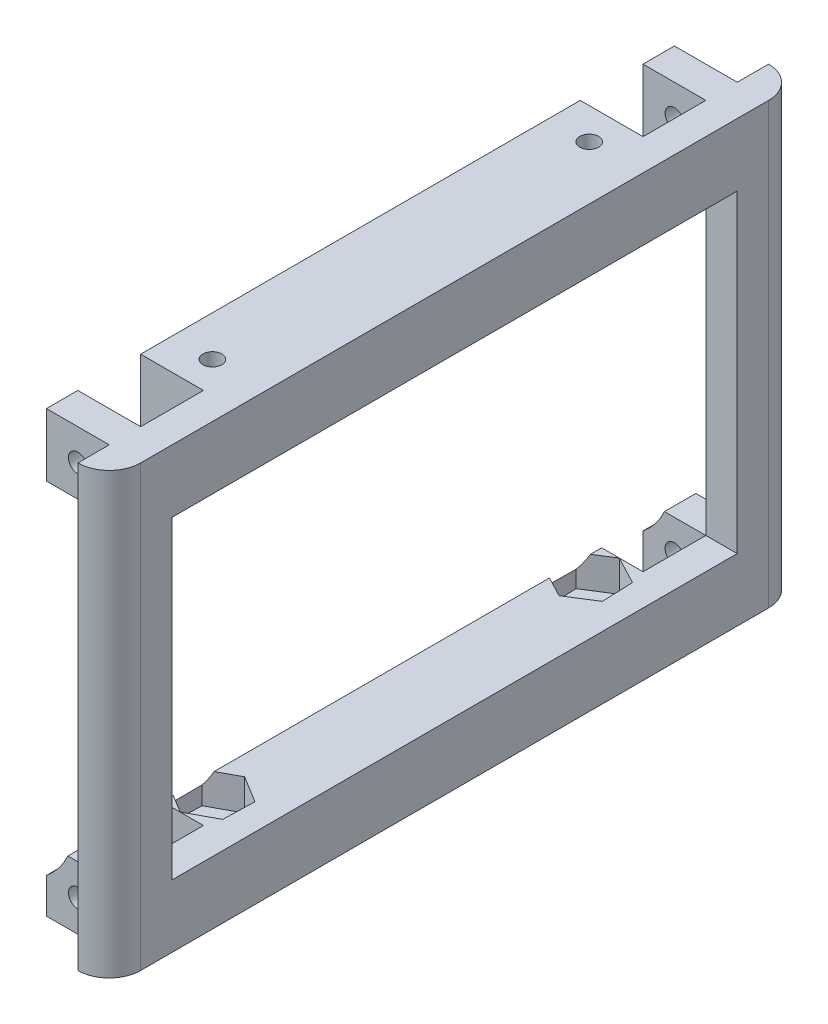
SolidWorks part; units mm, degrees
ref_plane "Front Plane" through (0, 0, 0) normal (0, 0, 1) x (1, 0, 0)
ref_plane "Top Plane" through (0, 0, 0) normal (0, 1, 0) x (1, 0, 0)
ref_plane "Right Plane" through (0, 0, 0) normal (1, 0, 0) x (0, 0, -1)
sketch "Sketch1" plane through (0, 0, 0) normal (1, 0, 0) x (0, 0, -1)
  line L1 (0, 0) -> (110, 0)
  line L2 (0, 0) -> (0, 70)
  line L3 (0, 70) -> (110, 70)
  line L4 (110, 0) -> (110, 70)
  dimension "D1" = 70
  dimension "D2" = 110
extrude "Boss-Extrude1" add sketch "Sketch1" along normal blind 5
fillet "Fillet2" radius 5 1 edges at (5, 35, 0) type face fillet first side face at (2.5, 35, 0) second side face at (5, 35, -55)
fillet "Fillet3" radius 5 1 edges at (5, 35, -110) type face fillet first side face at (5, 35, -57.5) second side face at (2.5, 35, -110)
sketch "Sketch2" plane through (0, 0, 0) normal (-1, 0, 0) x (0, 0, 1)
  line L1 (-105, 70) -> (-100, 70)
  line L2 (-105, 70) -> (-105, 60)
  line L3 (-105, 60) -> (-100, 60)
  line L4 (-100, 70) -> (-100, 60)
  line L5 (-105, 0) -> (-100, 0)
  line L6 (-105, 0) -> (-105, 10)
  line L7 (-105, 10) -> (-100, 10)
  line L8 (-100, 0) -> (-100, 10)
  line L9 (-5, 0) -> (-10, 0)
  line L10 (-5, 0) -> (-5, 10)
  line L11 (-5, 10) -> (-10, 10)
  line L12 (-10, 0) -> (-10, 10)
  line L13 (-5, 70) -> (-10, 70)
  line L14 (-5, 70) -> (-5, 60)
  line L15 (-5, 60) -> (-10, 60)
  line L16 (-10, 70) -> (-10, 60)
  dimension "D1" = 10
  dimension "D2" = 5
  dimension "D3" = 5
  dimension "D4" = 10
  dimension "D5" = 5
extrude "Boss-Extrude2" add sketch "Sketch2" along normal blind 10
sketch "Sketch3" plane through (0, 0, -5) normal (0, 0, 1) x (1, 0, 0)
  circle A0 centre (-5, 65) radius 1.5
  circle A1 centre (-5, 5) radius 1.5
  dimension "D1" = 3
  dimension "D2" = 3
extrude "Cut-Extrude1" cut sketch "Sketch3" against normal blind 122
sketch "Sketch4" plane through (0, 0, 0) normal (-1, 0, 0) x (0, 0, 1)
  line L0 (-100, 70) -> (-10, 70) construction
  line L1 (-90, 70) -> (-20, 70)
  line L2 (-90, 70) -> (-90, 60)
  line L3 (-90, 60) -> (-20, 60)
  line L4 (-20, 70) -> (-20, 60)
  line L5 (-10, 0) -> (-100, 0) construction
  line L6 (-90, 0) -> (-20, 0)
  line L7 (-90, 0) -> (-90, 10)
  line L8 (-90, 10) -> (-20, 10)
  line L9 (-20, 0) -> (-20, 10)
  dimension "D1" = 10
  dimension "D2" = 10
  dimension "D3" = 10
extrude "Boss-Extrude3" add sketch "Sketch4" along normal blind 10
sketch "Sketch5" plane through (0, 0, -5) normal (0, 0, 1) x (1, 0, 0)
  line L0 (-6.5, 5) -> (-17.5, 5) construction
  line L1 (-17.5, 5) -> (-17.5, 15) construction
  circle A0 centre (-5, 5) radius 1.5 construction
  circle A1 centre (-17.5, 15) radius 11.5
  dimension "D3" = 23
  dimension "D1" = 11
  dimension "D2" = 10
extrude "Cut-Extrude2" cut sketch "Sketch5" against normal blind 105
sketch "Sketch6" plane through (0, 0, 0) normal (0, -1, 0) x (1, 0, 0)
  line L1 (-10, -20) -> (0, -20) construction
  line L2 (-10, -90) -> (0, -90) construction
  circle A0 centre (-3.5738, -25) radius 1.5
  circle A1 centre (-3.5738, -85) radius 1.5
  point P9 (-5, -90)
  dimension "D2" = 3
  dimension "D4" = 3
  dimension "D1" = 3.57
  dimension "D3" = 5
  dimension "D5" = 5
extrude "Cut-Extrude3" cut sketch "Sketch6" against normal blind 105 contours A1 | A0
sketch "Sketch7" plane through (0, 60, 0) normal (0, -1, 0) x (1, 0, 0)
  line L1 (0.8247, -27.3775) -> (0.6844, -22.3795)
  line L2 (0.6844, -22.3795) -> (-3.7141, -20.002)
  line L3 (-3.7141, -20.002) -> (-7.9724, -22.6225)
  line L4 (-7.9724, -22.6225) -> (-7.8321, -27.6205)
  line L5 (-7.8321, -27.6205) -> (-3.4336, -29.998)
  line L6 (-3.4336, -29.998) -> (0.8247, -27.3775)
  line L7 (0.6549, -87.6679) -> (0.851, -82.6717)
  line L8 (0.851, -82.6717) -> (-3.3778, -80.0038)
  line L9 (-3.3778, -80.0038) -> (-7.8026, -82.3321)
  line L10 (-7.8026, -82.3321) -> (-7.9987, -87.3283)
  line L11 (-7.9987, -87.3283) -> (-3.7699, -89.9962)
  line L12 (-3.7699, -89.9962) -> (0.6549, -87.6679)
  circle A0 centre (-3.5738, -25) radius 4.3301 construction
  circle A1 centre (-3.5738, -85) radius 4.3301 construction
  point P1 (-7.9023, -25.1215)
  dimension "D1" = 2.5
  dimension "D2" = 5
extrude "Cut-Extrude4" cut sketch "Sketch7" along normal blind 55 and the other way blind 5
sketch "Sketch9" plane through (0, 0, 0) normal (-1, 0, 0) x (0, 0, 1)
  line L1 (-10, 10) -> (-100, 10)
  line L2 (-10, 10) -> (-10, 60)
  line L3 (-10, 60) -> (-100, 60)
  line L4 (-100, 10) -> (-100, 60)
extrude "Cut-Extrude5" cut sketch "Sketch9" against normal blind 55
sketch "Sketch10" plane through (0, 0, -5) normal (0, 0, 1) x (1, 0, 0)
  circle A0 centre (-17.5, 15) radius 12
  dimension "D1" = 24
extrude "Cut-Extrude6" cut sketch "Sketch10" against normal blind 109
